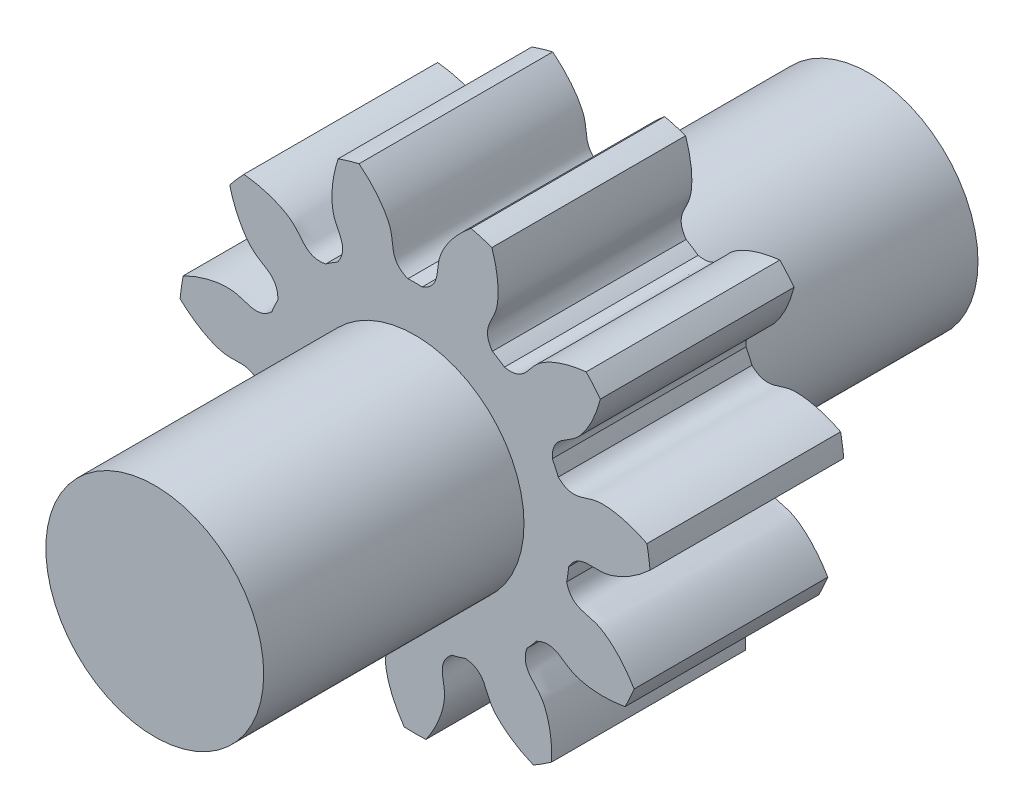
SolidWorks part; units mm, degrees
ref_plane "前视基准面" through (0, 0, 0) normal (0, 0, 1) x (1, 0, 0)
ref_plane "上视基准面" through (0, 0, 0) normal (0, 1, 0) x (1, 0, 0)
ref_plane "右视基准面" through (0, 0, 0) normal (1, 0, 0) x (0, 0, -1)
sketch "草图1" plane through (0, 0, 0) normal (0, 0, 1) x (1, 0, 0)
  circle A0 centre (0, 0) radius 19.5
extrude "凸台-拉伸1" add sketch "草图1" along normal blind 16
ref_axis "基准轴1" through (0, 0, -0.8) along (0, 0, 1)
sketch "草图2" plane through (0, 0, 0) normal (0, 0, 1) x (1, 0, 0)
  line L0 (0, 0) -> (0, 19.5) construction
  circle A0 centre (0, 0) radius 19.5 construction
  arc A1 (0.5902, 12.7363) -> (-0.5902, 12.7363) centre (0, 0) ccw
  arc A2 (10.9504, 21.8702) -> (-10.9504, 21.8702) centre (0, 0) ccw
  spline S0 degree 3 poles (0.5902, 12.7363) (2.1044, 13.3398) (1.7238, 14.574) (2.0472, 15.6226) (2.0657, 15.6786) (2.0873, 15.74) (2.1124, 15.8068) (2.141, 15.8788) (2.1736, 15.956) (2.2101, 16.0381) (2.251, 16.1252) (2.2963, 16.2169) (2.3463, 16.3133) (2.4011, 16.414) (2.4611, 16.5191) (2.5263, 16.6282) (2.597, 16.7413) (2.6733, 16.8581) (2.7554, 16.9785) (2.8435, 17.1023) (2.9378, 17.2293) (3.0384, 17.3593) (3.1455, 17.4921) (3.2591, 17.6275) (3.3796, 17.7652) (3.5069, 17.9051) (3.6413, 18.0469) (3.7829, 18.1904) (3.9317, 18.3354) (4.0879, 18.4816) (4.2517, 18.6288) (4.423, 18.7767) (4.6021, 18.9252) (4.7889, 19.0739) (4.9836, 19.2226) (5.1862, 19.3711) (5.3969, 19.519) (5.6156, 19.6662) (5.8424, 19.8123) (6.0773, 19.9571) (6.3205, 20.1003) (6.5719, 20.2417) (6.8315, 20.3809) (7.0994, 20.5178) (7.3755, 20.652) (7.6599, 20.7832) (7.9525, 20.9112) (8.2534, 21.0357) (8.5625, 21.1564) (8.8798, 21.2731) (9.2052, 21.3854) (9.5386, 21.493) (9.8801, 21.5958) (10.3501, 21.727) (10.7084, 21.8155) (10.9504, 21.8702) knots 0 0 0 0 0.219011 0.222642 0.226699 0.231184 0.236096 0.241435 0.247201 0.253394 0.260015 0.267062 0.274537 0.282438 0.290767 0.299523 0.308706 0.318316 0.328354 0.338818 0.34971 0.361028 0.372774 0.384947 0.397547 0.410574 0.424029 0.43791 0.452219 0.466954 0.482117 0.497707 0.513724 0.530168 0.547039 0.564338 0.582063 0.600216 0.618795 0.637802 0.657236 0.677097 0.697385 0.718101 0.739243 0.760813 0.782809 0.805233 0.828084 0.851362 0.875067 0.8992 0.923759 0.948746 1 1 1 1
  spline S1 degree 3 poles (-0.5902, 12.7363) (-2.1044, 13.3398) (-1.7238, 14.574) (-2.0472, 15.6226) (-2.0657, 15.6786) (-2.0873, 15.74) (-2.1124, 15.8068) (-2.141, 15.8788) (-2.1736, 15.956) (-2.2101, 16.0381) (-2.251, 16.1252) (-2.2963, 16.2169) (-2.3463, 16.3133) (-2.4011, 16.414) (-2.4611, 16.5191) (-2.5263, 16.6282) (-2.597, 16.7413) (-2.6733, 16.8581) (-2.7554, 16.9785) (-2.8435, 17.1023) (-2.9378, 17.2293) (-3.0384, 17.3593) (-3.1455, 17.4921) (-3.2591, 17.6275) (-3.3796, 17.7652) (-3.5069, 17.9051) (-3.6413, 18.0469) (-3.7829, 18.1904) (-3.9317, 18.3354) (-4.0879, 18.4816) (-4.2517, 18.6288) (-4.423, 18.7767) (-4.6021, 18.9252) (-4.7889, 19.0739) (-4.9836, 19.2226) (-5.1862, 19.3711) (-5.3969, 19.519) (-5.6156, 19.6662) (-5.8424, 19.8123) (-6.0773, 19.9571) (-6.3205, 20.1003) (-6.5719, 20.2417) (-6.8315, 20.3809) (-7.0994, 20.5178) (-7.3755, 20.652) (-7.6599, 20.7832) (-7.9525, 20.9112) (-8.2534, 21.0357) (-8.5625, 21.1564) (-8.8798, 21.2731) (-9.2052, 21.3854) (-9.5386, 21.493) (-9.8801, 21.5958) (-10.3501, 21.727) (-10.7084, 21.8155) (-10.9504, 21.8702) knots 0 0 0 0 0.219011 0.222642 0.226699 0.231184 0.236096 0.241435 0.247201 0.253394 0.260015 0.267062 0.274537 0.282438 0.290767 0.299523 0.308706 0.318316 0.328354 0.338818 0.34971 0.361028 0.372774 0.384947 0.397547 0.410574 0.424029 0.43791 0.452219 0.466954 0.482117 0.497707 0.513724 0.530168 0.547039 0.564338 0.582063 0.600216 0.618795 0.637802 0.657236 0.677097 0.697385 0.718101 0.739243 0.760813 0.782809 0.805233 0.828084 0.851362 0.875067 0.8992 0.923759 0.948746 1 1 1 1
extrude "切除-拉伸1" cut sketch "草图2" along normal through all
pattern_circular "阵列(圆周)1" count 11 every 32.727 about axis through (0, 0, -0.8) along (0, 0, 1) of "切除-拉伸1"
sketch "草图3" plane through (0, 0, 0) normal (0, 0, 1) x (1, 0, 0)
  circle A0 centre (0, 0) radius 16.5 construction
  dimension "Dn" = 33
sketch "草图4" plane through (0, 0, 16) normal (0, 0, 1) x (1, 0, 0)
  circle A0 centre (0, 0) radius 9
  dimension "D1" = 18
extrude "凸台-拉伸2" add sketch "草图4" along normal blind 21.5
sketch "草图5" plane through (0, 0, 37.5) normal (0, 0, 1) x (1, 0, 0)
  circle A1 centre (0, 0) radius 9
  circle A2 centre (0, 0) radius 9
  dimension "D1" = 0
extrude "凸台-拉伸3" add sketch "草图5" against normal blind 59
